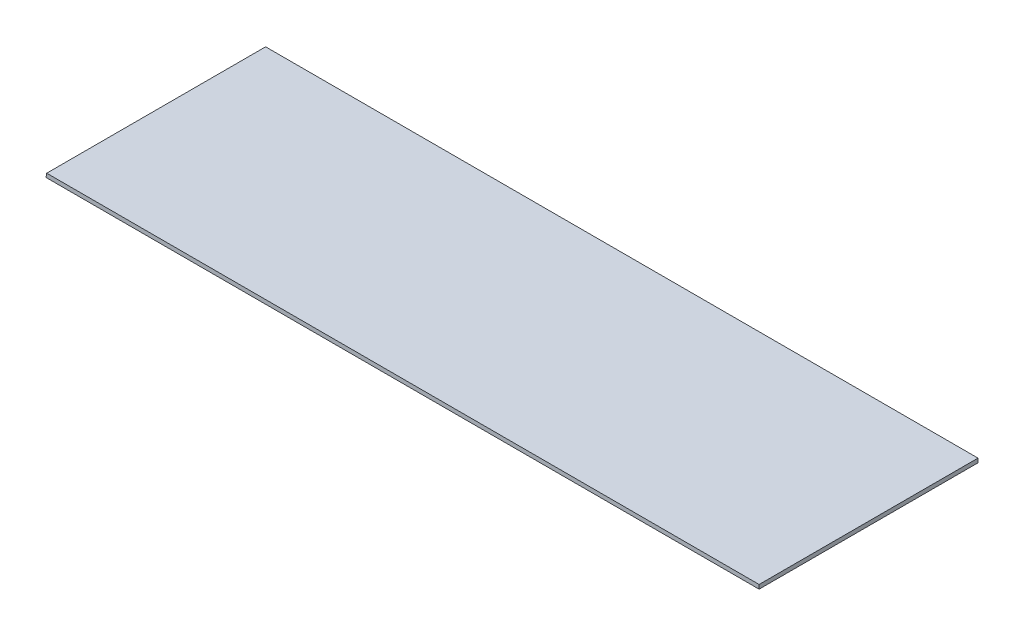
SolidWorks part; units mm, degrees
ref_plane "前视基准面" through (0, 0, 0) normal (0, 0, 1) x (1, 0, 0)
ref_plane "上视基准面" through (0, 0, 0) normal (0, 1, 0) x (1, 0, 0)
ref_plane "右视基准面" through (0, 0, 0) normal (1, 0, 0) x (0, 0, -1)
sketch "草图1" plane through (0, 0, 0) normal (0, 1, 0) x (1, 0, 0)
  line L1 (-42.0109, 83.894) -> (307.9891, 83.894)
  line L2 (-42.0109, 83.894) -> (-42.0109, -23.106)
  line L3 (-42.0109, -23.106) -> (307.9891, -23.106)
  line L4 (307.9891, 83.894) -> (307.9891, -23.106)
  dimension "D1" = 107
  dimension "D2" = 350
extrude "凸台-拉伸1" add sketch "草图1" along normal blind 2
chamfer "倒角1" distance 10 angle 10 1 edges at (-42.0109, 2, -30.394) first distance on face at (-42.0109, 1, -30.394)
